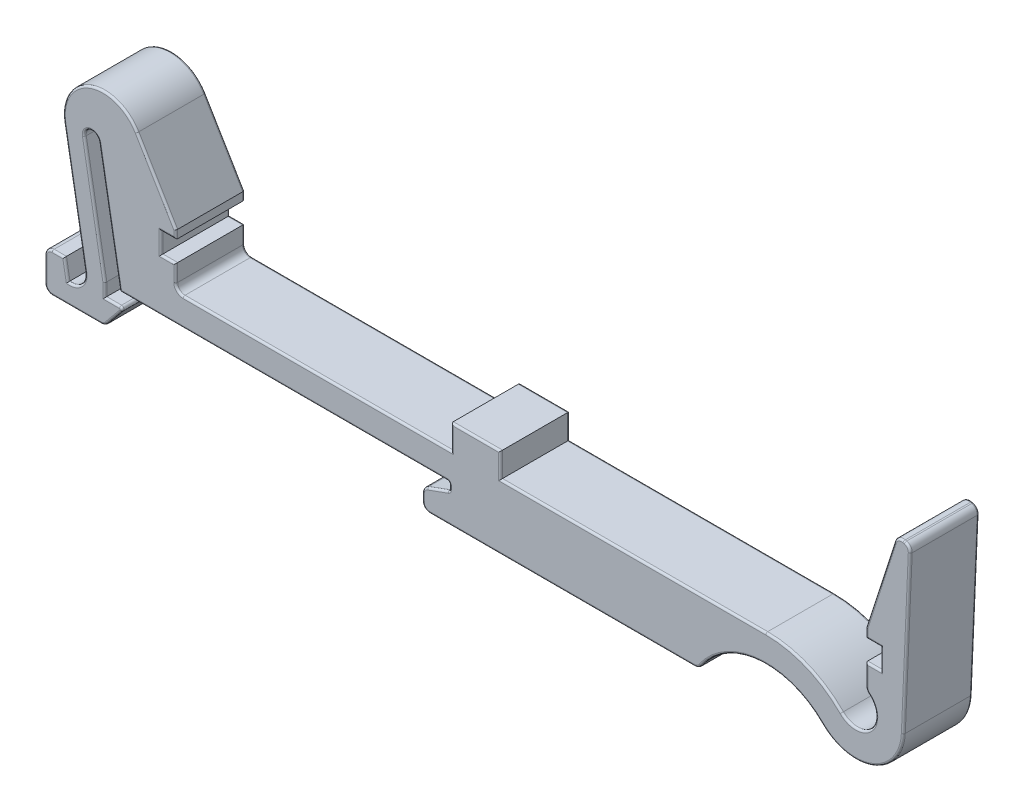
SolidWorks part; units mm, degrees
ref_plane "Front Plane" through (0, 0, 0) normal (0, 0, 1) x (1, 0, 0)
ref_plane "Top Plane" through (0, 0, 0) normal (0, 1, 0) x (1, 0, 0)
ref_plane "Right Plane" through (0, 0, 0) normal (1, 0, 0) x (0, 0, -1)
sketch "Sketch1" plane through (0, 0, 0) normal (0, 0, 1) x (1, 0, 0)
  line L0 (-6.797, 0.2) -> (-8.047, 0.2)
  line L1 (-6.797, 0.2) -> (-6.4443, -1.8)
  line L2 (-8.797, -0.55) -> (-8.797, -3.05)
  line L3 (-8.047, -3.8) -> (-3.0764, -3.8)
  line L4 (-2.4964, -3.5255) -> (-1.0067, -1.7085)
  line L6 (-1.2, -1.3) -> (-2.7, -1.3)
  line L7 (-2.7, -1.3) -> (-2.7, 0)
  line L8 (-2.7, 0) -> (-4.7838, 11.8177)
  line L9 (-3.3066, 12.0782) -> (-1.1769, 0)
  line L10 (-1.1769, 0) -> (32.05, 0)
  line L13 (32.3, -0.25) -> (32.3, -0.6249)
  line L14 (32.1355, -0.8599) -> (30.0435, -1.6213)
  line L15 (29.55, -2.3261) -> (29.55, -3.0509)
  line L16 (30.3, -3.8009) -> (57.195, -3.8009)
  line L17 (78.4091, 0.8288) -> (79.1111, 17.0699)
  line L18 (77.505, 17.3718) -> (74.6, 8.3666)
  line L19 (74.6, 8.3666) -> (74.6, 7.4)
  line L20 (74.6, 7.4) -> (76.1, 7.4)
  line L21 (76.1, 7.4) -> (76.1, 5.3)
  line L22 (76.1, 5.3) -> (74.6, 5.3)
  line L23 (74.6, 5.3) -> (74.6, 3.1885)
  line L24 (64.4362, 2.8) -> (5.25, 2.8)
  line L25 (4.5, 3.55) -> (4.5, 5.3)
  line L26 (4.5, 5.3) -> (3, 5.3)
  line L27 (3, 5.3) -> (3, 7.4)
  line L28 (3, 7.4) -> (4.5, 7.4)
  line L29 (4.5, 7.4) -> (4.5, 8.2271)
  line L30 (4.5, 8.2271) -> (0.5556, 14.8347)
  line L31 (-6.8599, 12.0743) -> (-4.7309, 0)
  line L35 (78.4118, 17.8654) -> (78.5559, 17.8268)
  arc A0 (-8.047, 0.2) -> (-8.797, -0.55) centre (-8.047, -0.55) ccw
  arc A1 (-8.797, -3.05) -> (-8.047, -3.8) centre (-8.047, -3.05) ccw
  arc A2 (-3.0764, -3.8) -> (-2.4964, -3.5255) centre (-3.0764, -3.05) ccw
  arc A3 (-1.0067, -1.7085) -> (-1.2, -1.3) centre (-1.2, -1.55) ccw
  arc A4 (-4.7838, 11.8177) -> (-3.3066, 12.0782) centre (-4.0452, 11.9479) cw
  arc A5 (32.05, 0) -> (32.3, -0.25) centre (32.05, -0.25) cw
  arc A6 (32.3, -0.6249) -> (32.1355, -0.8599) centre (32.05, -0.6249) cw
  arc A7 (30.0435, -1.6213) -> (29.55, -2.3261) centre (30.3, -2.3261) ccw
  arc A8 (29.55, -3.0509) -> (30.3, -3.8009) centre (30.3, -3.0509) ccw
  arc A9 (57.195, -3.8009) -> (57.8123, -3.4769) centre (57.195, -3.0509) ccw
  arc A10 (57.8123, -3.4769) -> (70.1435, -2.3738) centre (64.4362, -8.0481) cw
  arc A11 (70.1435, -2.3738) -> (78.4091, 0.8288) centre (73.5749, 1.0378) ccw
  arc A12 (79.1111, 17.0699) -> (78.5559, 17.8268) centre (78.3618, 17.1023) ccw
  arc A13 (78.4118, 17.8654) -> (77.505, 17.3718) centre (78.2179, 17.1418) ccw
  arc A14 (74.6, 3.1885) -> (74.8726, 2.6101) centre (75.35, 3.1885) ccw
  arc A15 (74.8726, 2.6101) -> (72.1291, -0.3996) centre (73.5749, 1.0378) cw
  arc A16 (64.4362, 2.8) -> (72.1291, -0.3996) centre (64.4362, -8.0481) cw
  arc A17 (5.25, 2.8) -> (4.5, 3.55) centre (5.25, 3.55) cw
  arc A18 (0.5556, 14.8347) -> (-6.8599, 12.0743) centre (-2.8984, 12.7728) ccw
  arc A19 (-4.7309, 0) -> (-6.4443, -1.8) centre (-6.2514, -0.2681) cw
  dimension "D1" = 35
  dimension "D2" = 73.1
  dimension "D3" = 1.5
extrude "Boss-Extrude1" add sketch "Sketch1" along normal blind 7
sketch "Sketch2" plane through (0, 0, 0) normal (0, 0, 1) x (1, 0, 0)
  line L1 (32.5, 2.8) -> (37.5, 2.8)
  line L2 (32.5, 2.8) -> (32.5, 5.3)
  line L3 (32.5, 5.3) -> (37.5, 5.3)
  line L4 (37.5, 2.8) -> (37.5, 5.3)
  line L5 (64.4362, 2.8) -> (5.25, 2.8) construction
  line L6 (4.5, 5.3) -> (3, 5.3) construction
  line L7 (3, 6.35) -> (76.1, 6.35) construction
  line L8 (3, 5.3) -> (3, 7.4) construction
  line L9 (76.1, 7.4) -> (76.1, 5.3) construction
  line L10 (39.55, 6.35) -> (39.55, 5.3) construction
  point P4 (35, 5.3)
  dimension "D1" = 5
  dimension "D2" = 32
extrude "Boss-Extrude2" add sketch "Sketch2" along normal up to surface (7 mm away) up to face at (28.7528, 3.2793, 7)
fillet "Fillet1" radius 0.2 108 edges at (-7.422, 0.2, 0) (-8.5773, -0.0197, 0) (-8.797, -1.8, 0) (-8.5773, -3.5803, 0) (-5.5617, -3.8, 0) (-2.7556, -3.7279, 0) (-1.7515, -2.617, 0) (-0.974, -1.4431, 0) (-1.95, -1.3, 0) (-2.7, -0.65, 0) (-3.7419, 5.9088, 0) (-4.1754, 12.6865, 0) (-2.2417, 6.0391, 0) (15.4366, 0, 0) (32.2268, -0.0732, 0) (32.3, -0.4375, 0) (32.2548, -0.7683, 0) (31.0895, -1.2406, 0) (29.6856, -1.8959, 0) (29.55, -2.6885, 0) (29.7697, -3.5812, 0) (43.7475, -3.8009, 0) (57.5436, -3.715, 0) (63.7191, -0.032, 0) (75.3231, -3.4741, 0) (78.7601, 8.9494, 0) (78.9665, 17.5459, 0) (78.4838, 17.8461, 0) (77.8598, 17.7998, 0) (76.0525, 12.8692, 0) (74.6, 7.8833, 0) (75.35, 7.4, 0) (76.1, 6.35, 0) (75.35, 5.3, 0) (74.6, 4.2443, 0) (74.6716, 2.8688, 0) (75.0816, -0.3356, 0) (68.6021, 1.9682, 0) (18.875, 2.8, 0) (50.9681, 2.8, 0) (4.7197, 3.0197, 0) (4.5, 4.425, 0) (3.75, 5.3, 0) (3, 6.35, 0) (3.75, 7.4, 0) (4.5, 7.8136, 0) (2.5278, 11.5309, 0) (-4.3017, 16.5427, 0) (-5.7954, 6.0372, 0) (-5.1331, -1.3327, 0) (-6.6206, -0.8, 0) (-5.1331, -1.3327, 7) (-5.7954, 6.0372, 7) (-4.3017, 16.5427, 7) (2.5278, 11.5309, 7) (4.5, 7.8136, 7) (3.75, 7.4, 7) (3, 6.35, 7) (3.75, 5.3, 7) (4.5, 4.425, 7) (4.7197, 3.0197, 7) (50.9681, 2.8, 7) (18.875, 2.8, 7) (68.6021, 1.9682, 7) (75.0816, -0.3356, 7) (74.6716, 2.8688, 7) (74.6, 4.2443, 7) (75.35, 5.3, 7) (76.1, 6.35, 7) (75.35, 7.4, 7) (74.6, 7.8833, 7) (76.0525, 12.8692, 7) (77.8598, 17.7998, 7) (78.4838, 17.8461, 7) (78.9665, 17.5459, 7) (78.7601, 8.9494, 7) (75.3231, -3.4741, 7) (63.7191, -0.032, 7) (57.5436, -3.715, 7) (43.7475, -3.8009, 7) (29.7697, -3.5812, 7) (29.55, -2.6885, 7) (29.6856, -1.8959, 7) (31.0895, -1.2406, 7) (32.2548, -0.7683, 7) (32.3, -0.4375, 7) (32.2268, -0.0732, 7) (15.4366, 0, 7) (-2.2417, 6.0391, 7) (-4.1754, 12.6865, 7) (-3.7419, 5.9088, 7) (-2.7, -0.65, 7) (-1.95, -1.3, 7) (-0.974, -1.4431, 7) (-1.7515, -2.617, 7) (-2.7556, -3.7279, 7) (-5.5617, -3.8, 7) (-8.5773, -3.5803, 7) (-8.797, -1.8, 7) (-8.5773, -0.0197, 7) (-7.422, 0.2, 7) (-6.6206, -0.8, 7) (37.5, 4.05, 0) (35, 5.3, 0) (32.5, 4.05, 0) (32.5, 4.05, 7) (35, 5.3, 7) (37.5, 4.05, 7)
